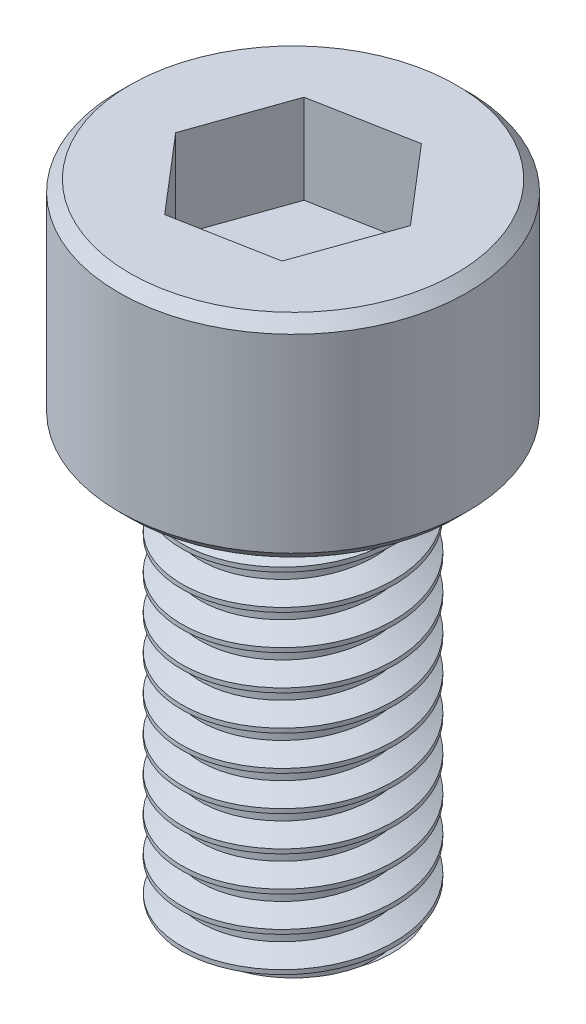
SolidWorks part; units mm, degrees
ref_plane "Front Plane" through (0, 0, 0) normal (0, 0, 1) x (1, 0, 0)
ref_plane "Top Plane" through (0, 0, 0) normal (0, 1, 0) x (1, 0, 0)
ref_plane "Right Plane" through (0, 0, 0) normal (1, 0, 0) x (0, 0, -1)
sketch "Sketch1" plane through (0, 0, 0) normal (0, 1, 0) x (1, 0, 0)
  circle A0 centre (0, 0) radius 3.9688
  dimension "D1" = 7.9375
extrude "Boss-Extrude1" add sketch "Sketch1" along normal blind 4.826
sketch "Sketch2" plane through (0, 4.826, 0) normal (0, 1, 0) x (1, 0, 0)
  line L1 (1.4906, -1.7403) -> (2.2524, 0.4208)
  line L2 (2.2524, 0.4208) -> (0.7618, 2.161)
  line L3 (0.7618, 2.161) -> (-1.4906, 1.7403)
  line L4 (-1.4906, 1.7403) -> (-2.2524, -0.4208)
  line L5 (-2.2524, -0.4208) -> (-0.7618, -2.161)
  line L6 (-0.7618, -2.161) -> (1.4906, -1.7403)
  circle A0 centre (0, 0) radius 1.9844 construction
  dimension "D1" = 3.9688
extrude "Cut-Extrude1" cut sketch "Sketch2" against normal blind 2.032
sketch "Sketch3" plane through (0, 0, 0) normal (0, -1, 0) x (1, 0, 0)
  circle A0 centre (0, 0) radius 2.413
  dimension "D1" = 4.826
extrude "Boss-Extrude2" add sketch "Sketch3" along normal blind 9.525
chamfer "Chamfer1" distance 0.254 angle 45 3 edges at (0, 4.826, 3.9688) (0, 0, 3.9688) (0, -9.525, -2.413)
thread "Thread1" pitch 0.7937 method cut profile "Thread Profile1" start angle 0, offset 1.27, length 0, pitch 0.7937, diameter 4.826
ref_plane "Plane1" through (2.413, -10.541, 0) normal (0, 0, 1) x (1, 0, 0)
sketch "Thread Profile1" plane through (2.413, -10.541, 0) normal (0, 0, 1) x (1, 0, 0)
  line L0 (0, 0) -> (0, 0.7937) construction
  line L11 (0, 0) -> (0, 0.6945)
  line L12 (0, 0.6945) -> (-0.4296, 0.4465)
  line L13 (-0.4296, 0.4465) -> (-0.4296, 0.248)
  line L15 (-0.4296, 0.248) -> (0, 0)
  line L17 (-0.4296, 0.3473) -> (0, 0.3473) construction
  point P2 (0, 0)
  dimension "Pitch" = 0.7937
  dimension "Profile_Angle" = 60
  dimension "Profile_Land" = 0.1984
  dimension "Profile_Height" = 0.4296
